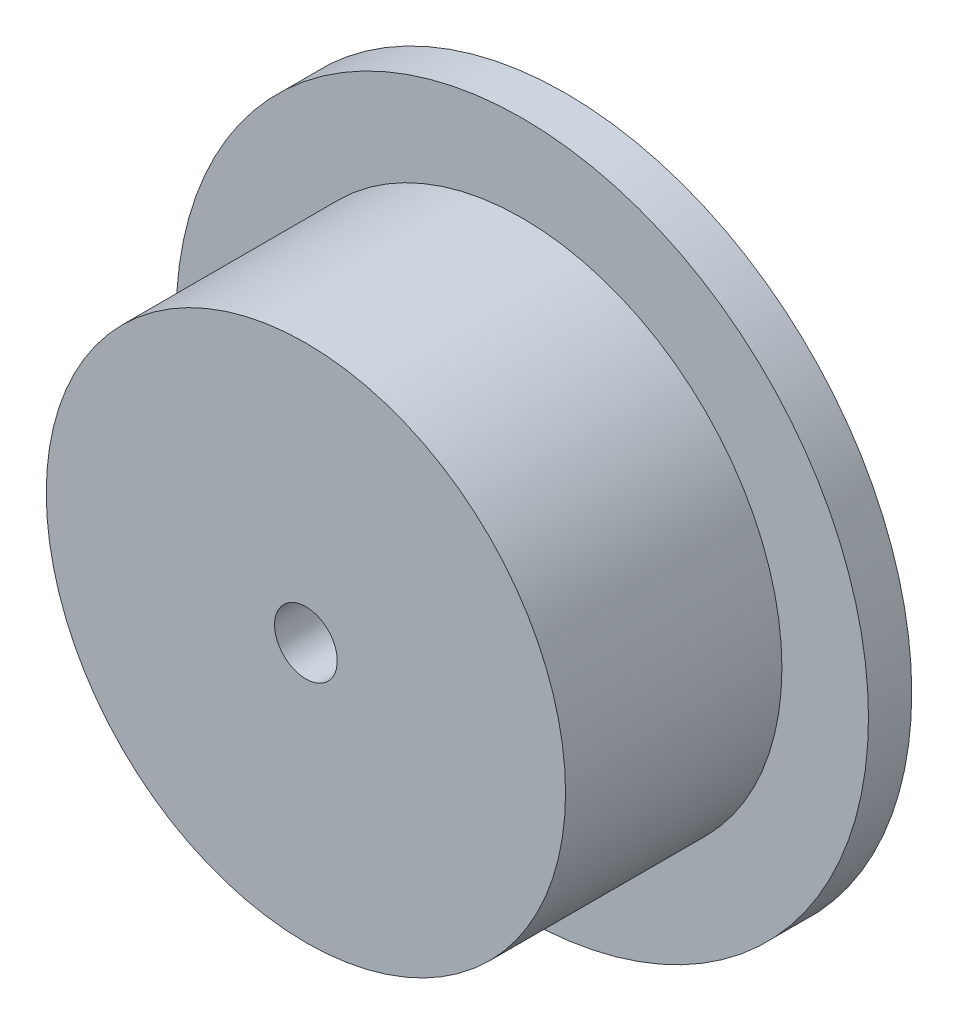
SolidWorks part; units mm, degrees
ref_plane "Front Plane" through (0, 0, 0) normal (0, 0, 1) x (1, 0, 0)
ref_plane "Top Plane" through (0, 0, 0) normal (0, 1, 0) x (1, 0, 0)
ref_plane "Right Plane" through (0, 0, 0) normal (1, 0, 0) x (0, 0, -1)
sketch "Sketch1" plane through (0, 0, 0) normal (0, 0, 1) x (1, 0, 0)
  circle A0 centre (0, 0) radius 12.7
  dimension "D1" = 25.4
extrude "Boss-Extrude1" add sketch "Sketch1" along normal blind 1.5875
sketch "Sketch2" plane through (0, 0, 1.5875) normal (0, 0, 1) x (1, 0, 0)
  circle A0 centre (0, 0) radius 9.525
  dimension "D1" = 19.05
extrude "Boss-Extrude2" add sketch "Sketch2" along normal blind 7.9375
sketch "Sketch3" plane through (0, 0, 9.525) normal (0, 0, 1) x (1, 0, 0)
  circle A0 centre (0, 0) radius 1.15
  dimension "D1" = 2.3
extrude "Cut-Extrude1" cut sketch "Sketch3" against normal through all
